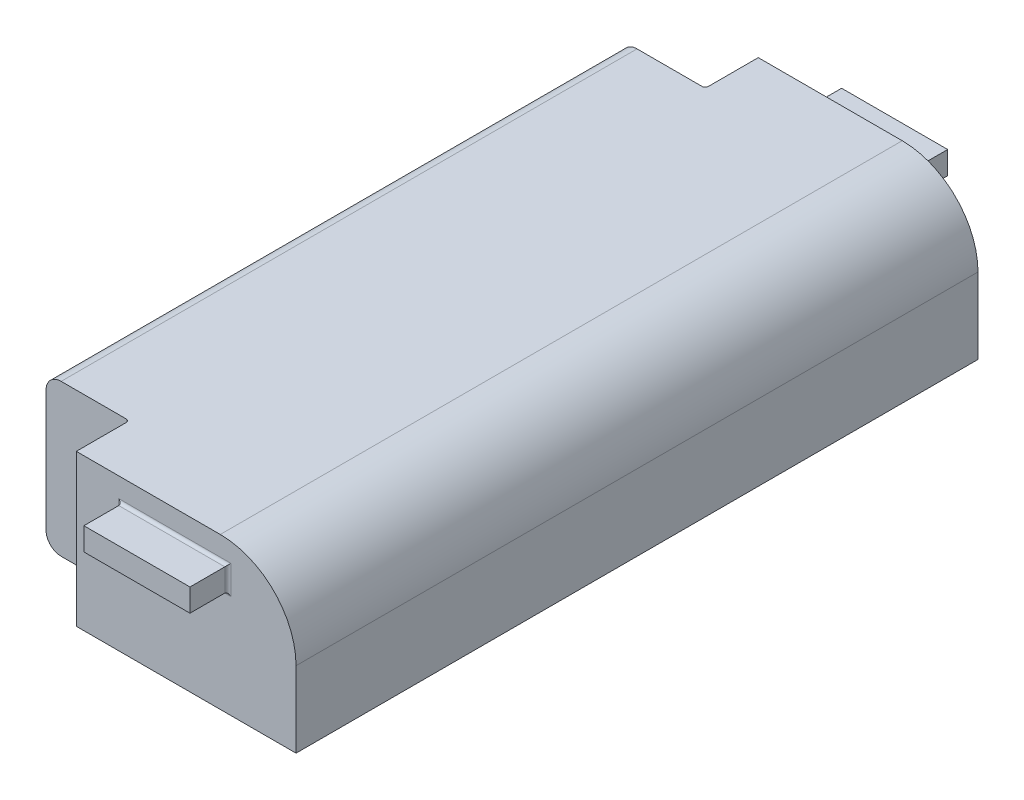
SolidWorks part; units mm, degrees
ref_plane "Front Plane" through (0, 0, 0) normal (0, 0, 1) x (1, 0, 0)
ref_plane "Top Plane" through (0, 0, 0) normal (0, 1, 0) x (1, 0, 0)
ref_plane "Right Plane" through (0, 0, 0) normal (1, 0, 0) x (0, 0, -1)
sketch "Sketch1" plane through (0, 0, 0) normal (0, 0, 1) x (1, 0, 0)
  line L0 (0, 0) -> (0, -19.05)
  line L1 (0, -19.05) -> (-7.62, -19.05)
  line L2 (-7.62, -19.05) -> (-7.62, 6.35)
  line L3 (-7.62, 6.35) -> (43.18, 6.35)
  line L4 (43.18, 6.35) -> (43.18, -19.05)
  line L7 (43.18, -19.05) -> (6.35, -19.05)
  line L8 (6.35, -19.05) -> (6.35, 0)
  line L9 (6.35, 0) -> (0, 0)
  dimension "D1" = 6.35
  dimension "D2" = 7.62
  dimension "D3" = 19.05
  dimension "D4" = 6.35
  dimension "D5" = 50.8
extrude "Boss-Extrude1" add sketch "Sketch1" along normal blind 96.52
ref_plane "Plane2" through (0, 0, 48.26) normal (0, 0, -1) x (-1, 0, 0)
sketch "Sketch3" plane through (0, 0, 96.52) normal (0, 0, 1) x (1, 0, 0)
  line L1 (6.35, -19.05) -> (43.18, -19.05)
  line L2 (6.35, -19.05) -> (6.35, 6.35)
  line L3 (6.35, 6.35) -> (43.18, 6.35)
  line L4 (43.18, -19.05) -> (43.18, 6.35)
extrude "Boss-Extrude3" add sketch "Sketch3" along normal blind 8.89
sketch "Sketch2" plane through (0, 0, 105.41) normal (0, 0, -1) x (-1, 0, 0)
  line L0 (-43.18, 6.35) -> (7.62, 6.35) construction
  line L1 (-31.75, -1.27) -> (-13.97, -1.27)
  line L2 (-31.75, -1.27) -> (-31.75, 2.54)
  line L3 (-31.75, 2.54) -> (-13.97, 2.54)
  line L4 (-13.97, -1.27) -> (-13.97, 2.54)
  line L6 (-6.35, 0) -> (-6.35, -19.05) construction
  dimension "D1" = 3.81
  dimension "D2" = 17.78
  dimension "D3" = 3.81
  dimension "D4" = 7.62
extrude "Boss-Extrude4" add sketch "Sketch2" against normal blind 6.35
mirror "Mirror2" about plane through (0, 0, 48.26) normal (0, 0, -1) of "Boss-Extrude3", "Boss-Extrude4"
fillet "Fillet1" radius 12.7 1 edges at (43.18, 6.35, 48.26)
fillet "Fillet2" radius 2.54 2 edges at (-7.62, -19.05, 48.26) (-7.62, 6.35, 48.26)
fillet "Fillet3" radius 0.508 12 edges at (6.35, 3.175, 0) (6.35, 3.175, 96.52) (13.97, 0.635, 105.41) (22.86, -1.27, 105.41) (22.86, 2.54, 105.41) (31.75, 0.635, 105.41) (13.97, 0.635, -8.89) (22.86, 2.54, -8.89) (31.75, 0.635, -8.89) (22.86, -1.27, -8.89) (0, 0, 48.26) (6.35, 0, 48.26)
